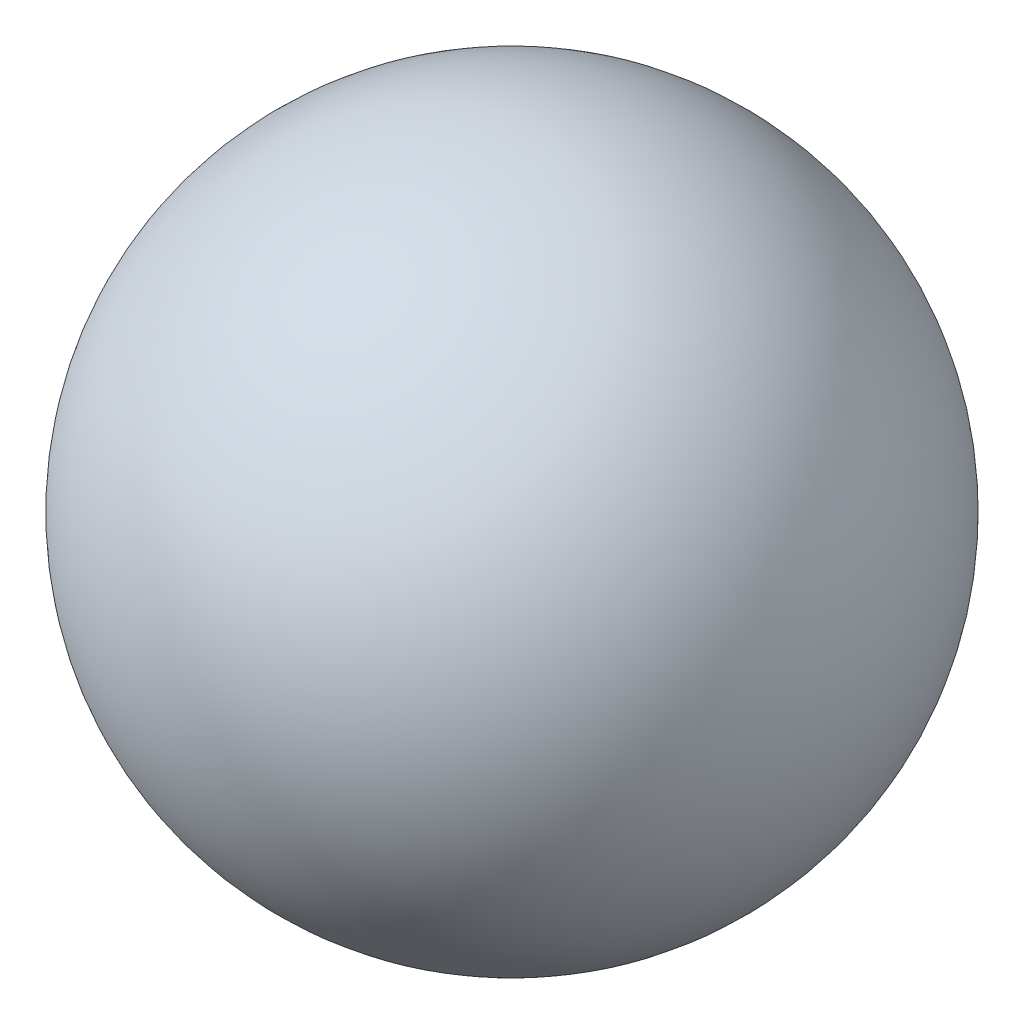
SolidWorks part; units mm, degrees
ref_plane "Front Plane" through (0, 0, 0) normal (0, 0, 1) x (1, 0, 0)
ref_plane "Top Plane" through (0, 0, 0) normal (0, 1, 0) x (1, 0, 0)
ref_plane "Right Plane" through (0, 0, 0) normal (1, 0, 0) x (0, 0, -1)
ref_axis "Axis1" through (0, -55, 0) along (0, 1, 0)
sketch "Sketch2" plane through (0, 0, 0) normal (0, 0, 1) x (1, 0, 0)
  line L0 (0, -55) -> (0, 55) construction
  line L1 (0, 200) -> (0, -200)
  arc A0 (0, 200) -> (0, -200) centre (0, 0) ccw
  dimension "D1" = 200
revolve "Revolve2" add sketch "Sketch2" angle 360 about axis through (0, -55, 0) along (0, 1, 0)
equation "\"radius\"=200"
equation "\"D1@Sketch2\"=\"radius\""
